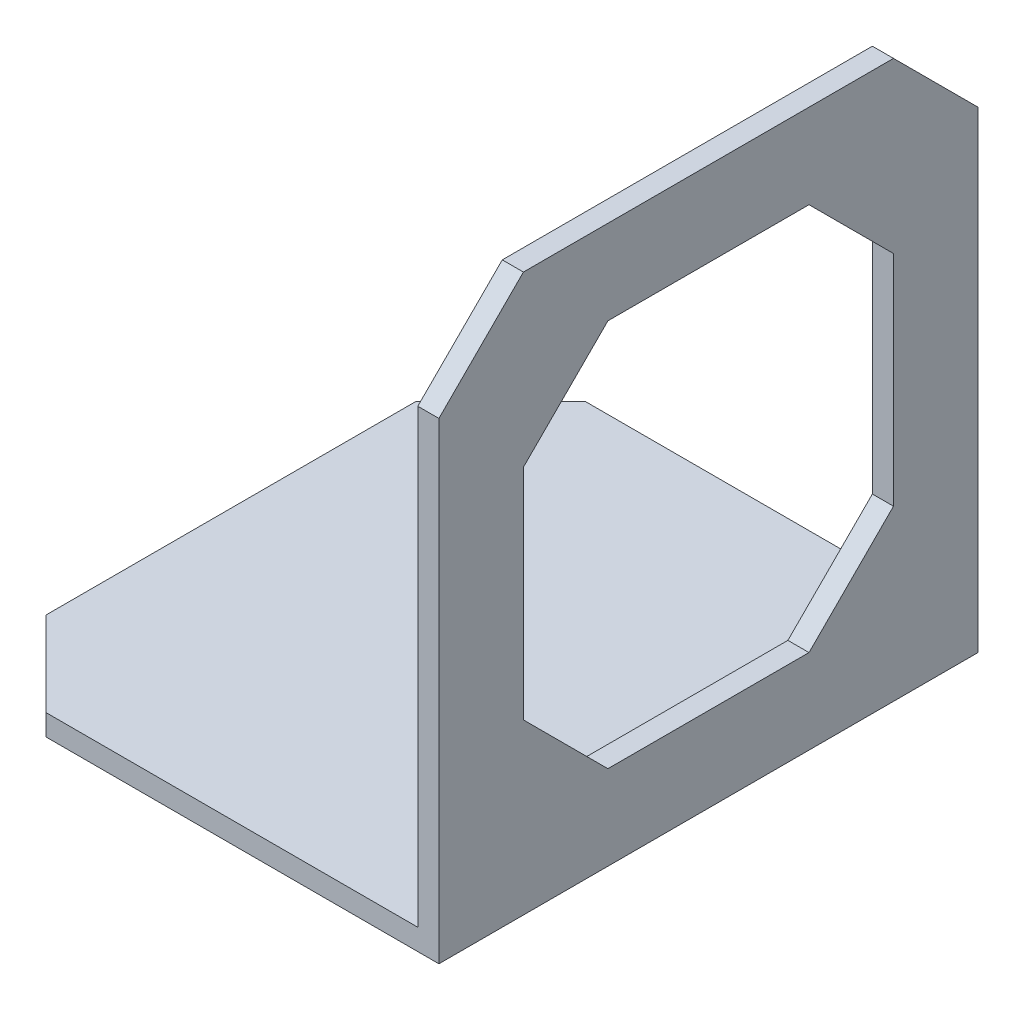
SolidWorks part; units mm, degrees
material "ABS PC"
ref_plane "Front Plane" through (0, 0, 0) normal (0, 0, 1) x (1, 0, 0)
ref_plane "Top Plane" through (0, 0, 0) normal (0, 1, 0) x (1, 0, 0)
ref_plane "Right Plane" through (0, 0, 0) normal (1, 0, 0) x (0, 0, -1)
sketch "Sketch1" plane through (0, 0, 0) normal (0, 1, 0) x (1, 0, 0)
  line L0 (0, 40.513) -> (71.755, 40.513) construction
  line L1 (0, 0) -> (71.755, 0)
  line L2 (0, 0) -> (0, 81.026)
  line L3 (0, 81.026) -> (71.755, 81.026)
  line L4 (71.755, 0) -> (71.755, 81.026)
  line L5 (35.8775, 81.026) -> (35.8775, 0) construction
  dimension "D1" = 71.755
  dimension "D2" = 81.026
extrude "Boss-Extrude1" add sketch "Sketch1" along normal blind 3.175
ref_plane "Plane2" through (0, 0, -40.513) normal (0, 0, -1) x (-1, 0, 0)
ref_plane "Plane1" through (35.8775, 0, 0) normal (1, 0, 0) x (0, 0, -1)
sketch "Sketch3" plane through (0, 3.175, 0) normal (0, 1, 0) x (1, 0, 0)
  line L0 (71.755, 0) -> (68.58, 0)
  line L1 (0, 0) -> (71.755, 0) construction
  line L2 (68.58, 0) -> (68.58, 81.026)
  line L3 (71.755, 81.026) -> (0, 81.026) construction
  line L4 (68.58, 81.026) -> (71.755, 81.026)
  line L5 (71.755, 81.026) -> (71.755, 0)
  dimension "D1" = 3.175
extrude "Boss-Extrude4" add sketch "Sketch3" along normal blind 80.518
sketch "Sketch8" plane through (0, 0, 0) normal (0, 0, 1) x (1, 0, 0)
  line L0 (27.4955, 0) -> (27.4955, -25.4)
  line L1 (0, 0) -> (71.755, 0) construction
  line L2 (44.2595, 0) -> (44.2595, -25.4)
  line L3 (44.2595, -25.4) -> (27.4955, -25.4)
  line L4 (27.4955, 0) -> (44.2595, 0)
  line L5 (35.8775, -1.7463) -> (35.8775, 1.7463) construction
  circle A1 centre (35.8775, -17.526) radius 2.3
  point P8 (35.8775, 0)
  point P11 (0, 0)
  point P12 (35.8775, -17.526)
  dimension "D3" = 7.874
  dimension "D4" = 4.5999
  dimension "D1" = 16.764
  dimension "D2" = 25.4
extrude "Boss-Extrude10" add sketch "Sketch8" along normal mid plane 12.6281 from surface contours L4 L2 L3 L0 | A1 starting at plane "Plane2"
fillet "Fillet1" radius 6.35 2 edges at (44.2595, -25.4, -40.513) (27.4955, -25.4, -40.513)
fillet "Fillet2" radius 8.4667 4 edges at (44.2595, 0, -40.513) (35.8775, 0, -34.1989) (27.4955, 0, -40.513) (35.8775, 0, -46.8271)
sketch "Sketch9" plane through (71.755, 0, 0) normal (1, 0, 0) x (0, 0, -1)
  line L0 (0, 83.693) -> (81.026, 0) construction
  line L1 (81.026, 83.693) -> (81.026, 0) construction
  line L2 (12.7, 12.7) -> (68.326, 12.7)
  line L3 (12.7, 12.7) -> (12.7, 70.993)
  line L4 (12.7, 70.993) -> (68.326, 70.993)
  line L5 (68.326, 12.7) -> (68.326, 70.993)
  line L6 (12.7, 12.7) -> (68.326, 70.993) construction
  line L7 (12.7, 70.993) -> (68.326, 12.7) construction
  line L8 (0, 83.693) -> (81.026, 83.693) construction
  point P4 (40.513, 41.8465)
  dimension "D1" = 12.7
  dimension "D2" = 12.7
extrude "Cut-Extrude1" cut sketch "Sketch9" against normal up to next contours L3 L2 L5 L4
fillet "Fillet3" radius 12.7 4 edges at (70.1675, 83.693, 0) (0, 1.5875, 0) (70.1675, 83.693, -81.026) (0, 1.5875, -81.026) profile chamfer
chamfer "Chamfer1" distance 12.7 angle 45 4 edges at (70.1675, 12.7, -12.7) (70.1675, 12.7, -68.326) (70.1675, 70.993, -68.326) (70.1675, 70.993, -12.7)
